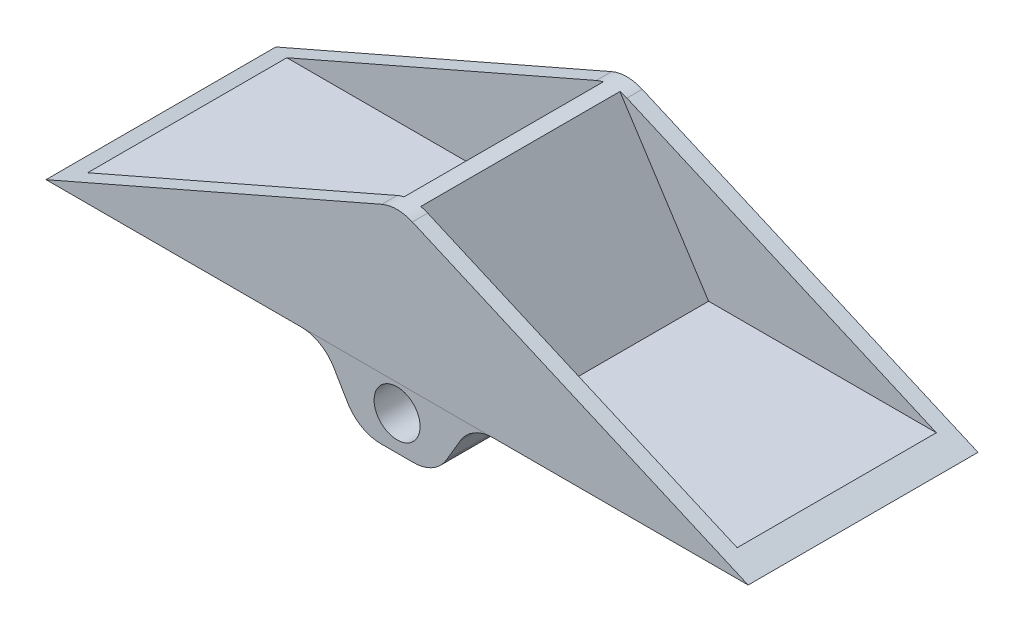
SolidWorks part; units mm, degrees
ref_plane "Plan de face" through (0, 0, 0) normal (0, 0, 1) x (1, 0, 0)
ref_plane "Plan de dessus" through (0, 0, 0) normal (0, 1, 0) x (1, 0, 0)
ref_plane "Plan de droite" through (0, 0, 0) normal (1, 0, 0) x (0, 0, -1)
sketch "Esquisse1" plane through (0, 0, 0) normal (0, 0, 1) x (1, 0, 0)
  line L0 (0, -8) -> (5, -8)
  line L1 (5, -8) -> (9.7068, 0)
  line L2 (9.7068, 0) -> (45.8258, 0)
  line L3 (45.8258, 0) -> (0, 20)
  line L4 (0, 20) -> (0, -8)
  dimension "D1" = 50
  dimension "D2" = 28
  dimension "D3" = 8
  dimension "D4" = 5
extrude "Boss.-Extru.1" add sketch "Esquisse1" along normal blind 30 contours L3 L4 L0 L1 L2
ref_plane "Plan1" through (0, 0, 2) normal (0, 0, 1) x (1, 0, 0)
sketch "Esquisse3" plane through (0, 0, 2) normal (0, 0, 1) x (1, 0, 0)
  line L0 (1, 19.5636) -> (12.6638, 1.5)
  line L1 (45.8258, 0) -> (0, 20) construction
  line L2 (12.6638, 1.5) -> (42.3888, 1.5)
  line L3 (42.3888, 1.5) -> (1, 19.5636)
  line L4 (9.7068, 0) -> (45.8258, 0) construction
  line L5 (0, 20) -> (0, -8) construction
  dimension "D1" = 1.5
  dimension "D2" = 1.5
  dimension "D3" = 1
extrude "Enlèv. mat.-Extru.1" cut sketch "Esquisse3" along normal blind 26 contours L3 L0 L2
fillet "Congé1" radius 5 1 edges at (5, -8, 15)
fillet "Congé2" radius 5 1 edges at (9.7068, 0, 15)
mirror "Symétrie1" about plane through (0, 0, 0) normal (1, 0, 0) of "Boss.-Extru.1", "Enlèv. mat.-Extru.1", "Congé1", "Congé2"
fillet "Congé3" radius 5 1 edges at (0, 20, 15)
sketch "Esquisse7" plane through (0, 0, 0) normal (0, 0, 1) x (1, 0, 0)
  line L0 (-2.1405, -8) -> (2.1405, -8) construction
  circle A0 centre (0, -3.5) radius 3
  point P2 (0, -8)
  dimension "D1" = 6
  dimension "D2" = 4.5
extrude "Enlèv. mat.-Extru.2" cut sketch "Esquisse7" along normal blind 30
sketch "Esquisse8" plane through (0, 0, 30) normal (0, 0, 1) x (1, 0, 0)
  line L0 (-12.5662, 0) -> (12.1754, -0.0153)
  arc A0 (12.5662, 0) -> (8.2568, -2.4645) centre (12.5662, -5) ccw construction
surface "Surface-Extrusion1" sketch "Esquisse8" parameters "D1"=40
split "Fractionner1" trimming surface bodies 106 bodies to split 105 resulting bodies 107 108
